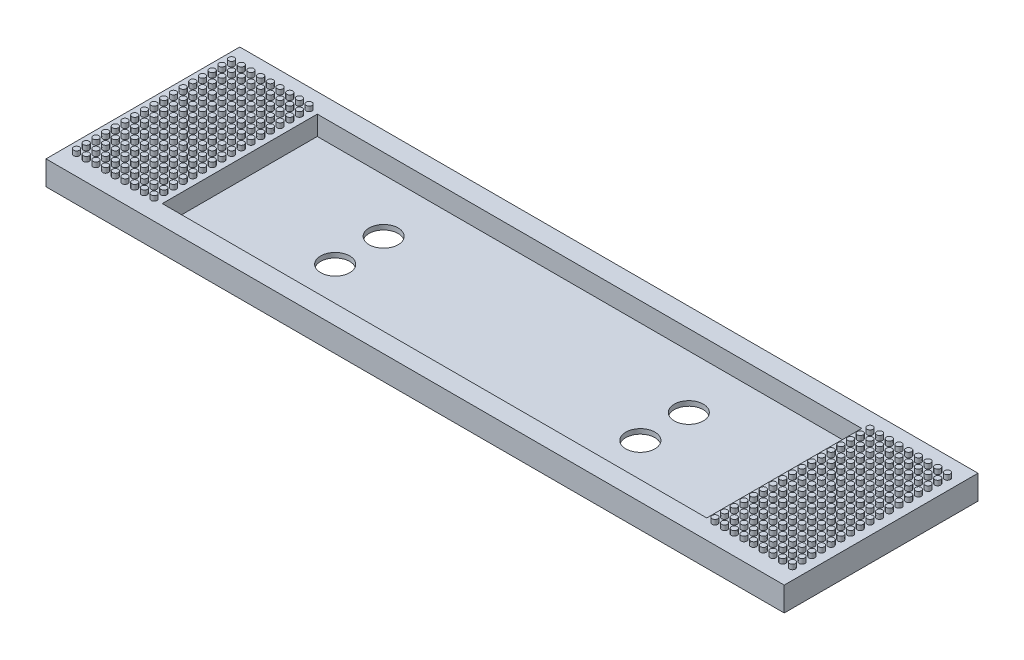
SolidWorks part; units mm, degrees
material "Stainless Steel (ferritic)"
ref_plane "Front Plane" through (0, 0, 0) normal (0, 0, 1) x (1, 0, 0)
ref_plane "Top Plane" through (0, 0, 0) normal (0, 1, 0) x (1, 0, 0)
ref_plane "Right Plane" through (0, 0, 0) normal (1, 0, 0) x (0, 0, -1)
sketch "Sketch1" plane through (0, 0, 0) normal (0, 1, 0) x (1, 0, 0)
  line L1 (0, 0) -> (193.548, 0)
  line L2 (0, 0) -> (0, 50.8)
  line L3 (0, 50.8) -> (193.548, 50.8)
  line L4 (193.548, 0) -> (193.548, 50.8)
  line L5 (25.4, 45.72) -> (168.148, 45.72)
  line L6 (25.4, 45.72) -> (25.4, 5.08)
  line L7 (25.4, 5.08) -> (168.148, 5.08)
  line L8 (168.148, 45.72) -> (168.148, 5.08)
  point P9 (0, 25.4)
  point P10 (25.4, 25.4)
  dimension "D1" = 193.548
  dimension "D2" = 50.8
  dimension "D3" = 25.4
  dimension "D4" = 25.4
  dimension "D5" = 5.08
extrude "Boss-Extrude1" add sketch "Sketch1" along normal blind 6.35 contours L2 L1 L4 L3
sketch "Sketch4" plane through (0, 6.35, 0) normal (0, 1, 0) x (1, 0, 0)
  line L0 (0, 50.8) -> (193.548, 50.8) construction
  line L1 (25.4, 45.72) -> (168.148, 45.72)
  line L2 (25.4, 45.72) -> (25.4, 5.08)
  line L3 (25.4, 5.08) -> (168.148, 5.08)
  line L4 (168.148, 45.72) -> (168.148, 5.08)
  line L5 (0, 0) -> (0, 50.8) construction
  point P8 (0, 25.4)
  point P9 (25.4, 25.4)
  point P10 (96.774, 45.72)
  point P11 (96.774, 50.8)
  dimension "D1" = 5.08
  dimension "D2" = 25.4
extrude "Cut-Extrude2" cut sketch "Sketch4" against normal blind 5.08
sketch "Sketch5" plane through (0, 6.35, 0) normal (0, 1, 0) x (1, 0, 0)
  line L0 (25.4, 45.72) -> (25.4, 5.08) construction
  line L1 (96.774, 50.8) -> (96.774, 0) construction
  line L2 (0, 50.8) -> (193.548, 50.8) construction
  line L3 (0, 0) -> (193.548, 0) construction
  circle A0 centre (2.9371, 45.72) radius 0.762
  circle A1 centre (5.4771, 45.72) radius 0.762
  circle A2 centre (8.0171, 45.72) radius 0.762
  circle A3 centre (10.5571, 45.72) radius 0.762
  circle A4 centre (13.0971, 45.72) radius 0.762
  circle A5 centre (15.6371, 45.72) radius 0.762
  circle A6 centre (18.1771, 45.72) radius 0.762
  circle A7 centre (20.7171, 45.72) radius 0.762
  circle A8 centre (23.2571, 45.72) radius 0.762
  circle A9 centre (5.4771, 43.18) radius 0.762
  circle A10 centre (8.0171, 43.18) radius 0.762
  circle A11 centre (10.5571, 43.18) radius 0.762
  circle A12 centre (13.0971, 43.18) radius 0.762
  circle A13 centre (15.6371, 43.18) radius 0.762
  circle A14 centre (18.1771, 43.18) radius 0.762
  circle A15 centre (20.7171, 43.18) radius 0.762
  circle A16 centre (23.2571, 43.18) radius 0.762
  circle A17 centre (5.4771, 40.64) radius 0.762
  circle A18 centre (8.0171, 40.64) radius 0.762
  circle A19 centre (10.5571, 40.64) radius 0.762
  circle A20 centre (13.0971, 40.64) radius 0.762
  circle A21 centre (15.6371, 40.64) radius 0.762
  circle A22 centre (18.1771, 40.64) radius 0.762
  circle A23 centre (20.7171, 40.64) radius 0.762
  circle A24 centre (23.2571, 40.64) radius 0.762
  circle A25 centre (5.4771, 38.1) radius 0.762
  circle A26 centre (8.0171, 38.1) radius 0.762
  circle A27 centre (10.5571, 38.1) radius 0.762
  circle A28 centre (13.0971, 38.1) radius 0.762
  circle A29 centre (15.6371, 38.1) radius 0.762
  circle A30 centre (18.1771, 38.1) radius 0.762
  circle A31 centre (20.7171, 38.1) radius 0.762
  circle A32 centre (23.2571, 38.1) radius 0.762
  circle A33 centre (5.4771, 35.56) radius 0.762
  circle A34 centre (8.0171, 35.56) radius 0.762
  circle A35 centre (10.5571, 35.56) radius 0.762
  circle A36 centre (13.0971, 35.56) radius 0.762
  circle A37 centre (15.6371, 35.56) radius 0.762
  circle A38 centre (18.1771, 35.56) radius 0.762
  circle A39 centre (20.7171, 35.56) radius 0.762
  circle A40 centre (23.2571, 35.56) radius 0.762
  circle A41 centre (5.4771, 33.02) radius 0.762
  circle A42 centre (8.0171, 33.02) radius 0.762
  circle A43 centre (10.5571, 33.02) radius 0.762
  circle A44 centre (13.0971, 33.02) radius 0.762
  circle A45 centre (15.6371, 33.02) radius 0.762
  circle A46 centre (18.1771, 33.02) radius 0.762
  circle A47 centre (20.7171, 33.02) radius 0.762
  circle A48 centre (23.2571, 33.02) radius 0.762
  circle A49 centre (5.4771, 30.48) radius 0.762
  circle A50 centre (8.0171, 30.48) radius 0.762
  circle A51 centre (10.5571, 30.48) radius 0.762
  circle A52 centre (13.0971, 30.48) radius 0.762
  circle A53 centre (15.6371, 30.48) radius 0.762
  circle A54 centre (18.1771, 30.48) radius 0.762
  circle A55 centre (20.7171, 30.48) radius 0.762
  circle A56 centre (23.2571, 30.48) radius 0.762
  circle A57 centre (5.4771, 27.94) radius 0.762
  circle A58 centre (8.0171, 27.94) radius 0.762
  circle A59 centre (10.5571, 27.94) radius 0.762
  circle A60 centre (13.0971, 27.94) radius 0.762
  circle A61 centre (15.6371, 27.94) radius 0.762
  circle A62 centre (18.1771, 27.94) radius 0.762
  circle A63 centre (20.7171, 27.94) radius 0.762
  circle A64 centre (23.2571, 27.94) radius 0.762
  circle A65 centre (5.4771, 25.4) radius 0.762
  circle A66 centre (8.0171, 25.4) radius 0.762
  circle A67 centre (10.5571, 25.4) radius 0.762
  circle A68 centre (13.0971, 25.4) radius 0.762
  circle A69 centre (15.6371, 25.4) radius 0.762
  circle A70 centre (18.1771, 25.4) radius 0.762
  circle A71 centre (20.7171, 25.4) radius 0.762
  circle A72 centre (23.2571, 25.4) radius 0.762
  circle A73 centre (5.4771, 22.86) radius 0.762
  circle A74 centre (8.0171, 22.86) radius 0.762
  circle A75 centre (10.5571, 22.86) radius 0.762
  circle A76 centre (13.0971, 22.86) radius 0.762
  circle A77 centre (15.6371, 22.86) radius 0.762
  circle A78 centre (18.1771, 22.86) radius 0.762
  circle A79 centre (20.7171, 22.86) radius 0.762
  circle A80 centre (23.2571, 22.86) radius 0.762
  circle A81 centre (5.4771, 20.32) radius 0.762
  circle A82 centre (8.0171, 20.32) radius 0.762
  circle A83 centre (10.5571, 20.32) radius 0.762
  circle A84 centre (13.0971, 20.32) radius 0.762
  circle A85 centre (15.6371, 20.32) radius 0.762
  circle A86 centre (18.1771, 20.32) radius 0.762
  circle A87 centre (20.7171, 20.32) radius 0.762
  circle A88 centre (23.2571, 20.32) radius 0.762
  circle A89 centre (5.4771, 17.78) radius 0.762
  circle A90 centre (8.0171, 17.78) radius 0.762
  circle A91 centre (10.5571, 17.78) radius 0.762
  circle A92 centre (13.0971, 17.78) radius 0.762
  circle A93 centre (15.6371, 17.78) radius 0.762
  circle A94 centre (18.1771, 17.78) radius 0.762
  circle A95 centre (20.7171, 17.78) radius 0.762
  circle A96 centre (23.2571, 17.78) radius 0.762
  circle A97 centre (5.4771, 15.24) radius 0.762
  circle A98 centre (8.0171, 15.24) radius 0.762
  circle A99 centre (10.5571, 15.24) radius 0.762
  circle A100 centre (13.0971, 15.24) radius 0.762
  circle A101 centre (15.6371, 15.24) radius 0.762
  circle A102 centre (18.1771, 15.24) radius 0.762
  circle A103 centre (20.7171, 15.24) radius 0.762
  circle A104 centre (23.2571, 15.24) radius 0.762
  circle A105 centre (5.4771, 12.7) radius 0.762
  circle A106 centre (8.0171, 12.7) radius 0.762
  circle A107 centre (10.5571, 12.7) radius 0.762
  circle A108 centre (13.0971, 12.7) radius 0.762
  circle A109 centre (15.6371, 12.7) radius 0.762
  circle A110 centre (18.1771, 12.7) radius 0.762
  circle A111 centre (20.7171, 12.7) radius 0.762
  circle A112 centre (23.2571, 12.7) radius 0.762
  circle A113 centre (5.4771, 10.16) radius 0.762
  circle A114 centre (8.0171, 10.16) radius 0.762
  circle A115 centre (10.5571, 10.16) radius 0.762
  circle A116 centre (13.0971, 10.16) radius 0.762
  circle A117 centre (15.6371, 10.16) radius 0.762
  circle A118 centre (18.1771, 10.16) radius 0.762
  circle A119 centre (20.7171, 10.16) radius 0.762
  circle A120 centre (23.2571, 10.16) radius 0.762
  circle A121 centre (5.4771, 7.62) radius 0.762
  circle A122 centre (8.0171, 7.62) radius 0.762
  circle A123 centre (10.5571, 7.62) radius 0.762
  circle A124 centre (13.0971, 7.62) radius 0.762
  circle A125 centre (15.6371, 7.62) radius 0.762
  circle A126 centre (18.1771, 7.62) radius 0.762
  circle A127 centre (20.7171, 7.62) radius 0.762
  circle A128 centre (23.2571, 7.62) radius 0.762
  circle A129 centre (5.4771, 5.08) radius 0.762
  circle A130 centre (8.0171, 5.08) radius 0.762
  circle A131 centre (10.5571, 5.08) radius 0.762
  circle A132 centre (13.0971, 5.08) radius 0.762
  circle A133 centre (15.6371, 5.08) radius 0.762
  circle A134 centre (18.1771, 5.08) radius 0.762
  circle A135 centre (20.7171, 5.08) radius 0.762
  circle A136 centre (23.2571, 5.08) radius 0.762
  circle A137 centre (2.9371, 43.18) radius 0.762
  circle A138 centre (2.9371, 40.64) radius 0.762
  circle A139 centre (2.9371, 38.1) radius 0.762
  circle A140 centre (2.9371, 35.56) radius 0.762
  circle A141 centre (2.9371, 33.02) radius 0.762
  circle A142 centre (2.9371, 30.48) radius 0.762
  circle A143 centre (2.9371, 27.94) radius 0.762
  circle A144 centre (2.9371, 25.4) radius 0.762
  circle A145 centre (2.9371, 22.86) radius 0.762
  circle A146 centre (2.9371, 20.32) radius 0.762
  circle A147 centre (2.9371, 17.78) radius 0.762
  circle A148 centre (2.9371, 15.24) radius 0.762
  circle A149 centre (2.9371, 12.7) radius 0.762
  circle A150 centre (2.9371, 10.16) radius 0.762
  circle A151 centre (2.9371, 7.62) radius 0.762
  circle A152 centre (2.9371, 5.08) radius 0.762
  point P309 (25.4, 25.4)
  dimension "D1" = 9
  dimension "D2" = 17
extrude "Boss-Extrude2" add sketch "Sketch5" along normal blind 1.27
ref_plane "Plane1" through (96.774, 0, 0) normal (1, 0, 0) x (0, 0, -1)
mirror "Mirror1" about plane through (96.774, 0, 0) normal (1, 0, 0) of "Boss-Extrude2"
sketch "Sketch6" plane through (0, 0, 0) normal (0, -1, 0) x (1, 0, 0)
  line L0 (0, -25.4) -> (193.548, -25.4) construction
  line L1 (0, 0) -> (0, -50.8) construction
  line L2 (193.548, 0) -> (193.548, -50.8) construction
  line L3 (96.774, -50.8) -> (96.774, 0) construction
  line L4 (0, -50.8) -> (193.548, -50.8) construction
  line L5 (0, 0) -> (193.548, 0) construction
  line L6 (56.769, -31.75) -> (56.769, -19.05) construction
  circle A0 centre (56.769, -31.75) radius 3.81
  circle A1 centre (56.769, -19.05) radius 3.81
  point P12 (96.774, -25.4)
  point P15 (56.769, -25.4)
  dimension "D2" = 7.62
  dimension "D3" = 7.62
  dimension "D1" = 12.7
  dimension "D4" = 40.005
extrude "Cut-Extrude3" cut sketch "Sketch6" against normal through all contours A0 | A1
cosmetic thread "Cosmetic Thread1" parameters "D2"=9.525
cosmetic thread "Cosmetic Thread2" parameters "D2"=9.525
mirror "Mirror3" about plane through (96.774, 0, 0) normal (1, 0, 0) of "Cut-Extrude3"
cosmetic thread "Cosmetic Thread3" parameters "D2"=9.525
cosmetic thread "Cosmetic Thread4" parameters "D2"=9.525
